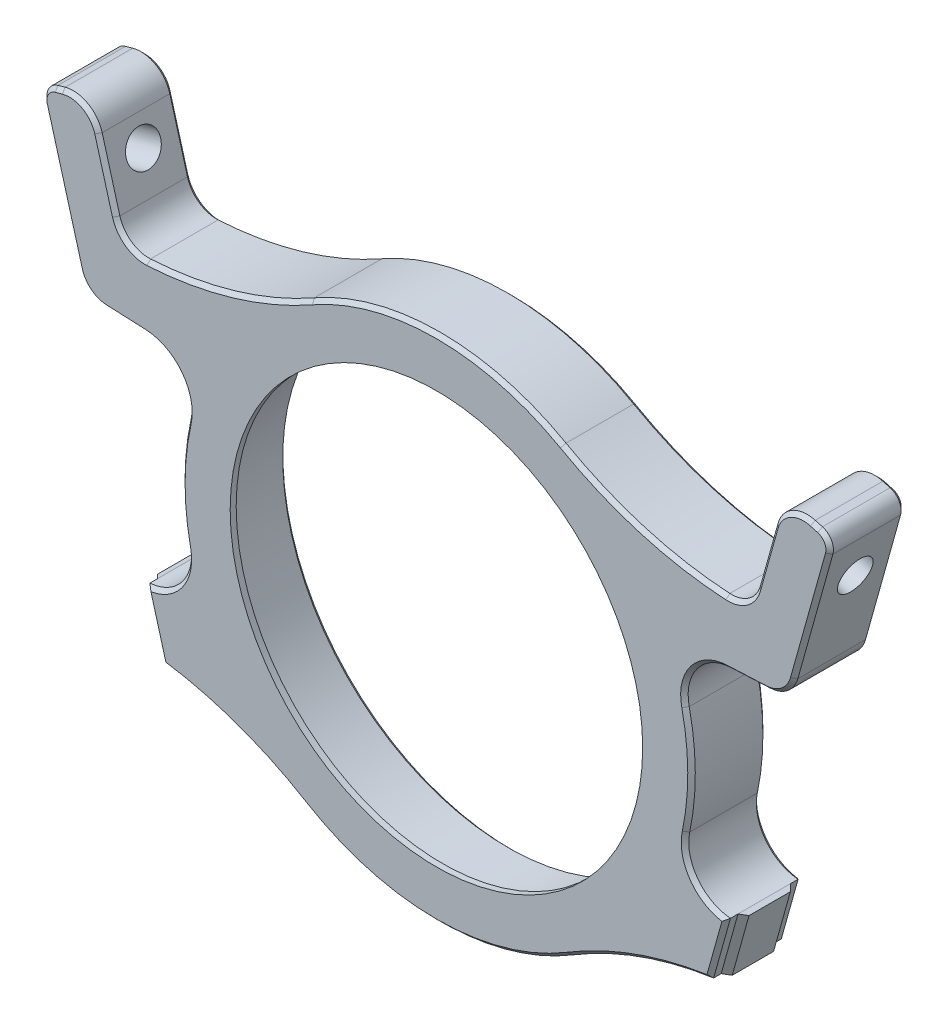
SolidWorks part; units mm, degrees
ref_plane "Ebene vorne" through (0, 0, 0) normal (0, 0, 1) x (1, 0, 0)
ref_plane "Ebene oben" through (0, 0, 0) normal (0, 1, 0) x (1, 0, 0)
ref_plane "Ebene rechts" through (0, 0, 0) normal (1, 0, 0) x (0, 0, -1)
sketch "Skizze1" plane through (0, 0, 0) normal (0, 0, 1) x (1, 0, 0)
  line L0 (-25.6051, -22.2931) -> (-36.3964, -22.2931)
  line L5 (-80.7379, 136.3891) -> (0, -152.5424) construction
  line L6 (-36.3964, -22.2931) -> (-38.6319, -14.2931)
  line L7 (-38.6319, -14.2931) -> (-30.7947, -14.2931)
  line L8 (0, 0) -> (-26.219, 0) construction
  line L9 (0, 0) -> (0, -14.2745) construction
  line L10 (38.6319, -14.2931) -> (30.7947, -14.2931)
  line L11 (36.3964, -22.2931) -> (38.6319, -14.2931)
  line L12 (25.6051, -22.2931) -> (36.3964, -22.2931)
  line L13 (-46.8229, 15.0197) -> (-30.7947, 14.2931)
  line L14 (-25.6051, 22.2931) -> (-41.7923, 23.027)
  line L15 (-46.8229, 15.0197) -> (-49.0328, 22.928)
  line L16 (25.6051, 22.2931) -> (41.7923, 23.027)
  line L17 (46.8229, 15.0197) -> (49.0328, 22.928)
  line L18 (46.8229, 15.0197) -> (30.7947, 14.2931)
  line L19 (80.7379, 136.3891) -> (0, -152.5424) construction
  line L20 (49.0328, 22.928) -> (52.8005, 36.4115)
  line L21 (52.8005, 36.4115) -> (46.0588, 38.2954)
  line L22 (46.0588, 38.2954) -> (41.7923, 23.027)
  line L23 (-49.0328, 22.928) -> (-52.8005, 36.4115)
  line L24 (-52.8005, 36.4115) -> (-46.0588, 38.2954)
  line L25 (-46.0588, 38.2954) -> (-41.7923, 23.027)
  line L26 (52.8005, 36.4115) -> (0, -152.5424) construction
  line L27 (-52.8005, 36.4115) -> (0, -152.5424) construction
  circle A0 centre (0, 0) radius 29.95
  arc A1 (-25.6051, -22.2931) -> (25.6051, -22.2931) centre (0, 0) ccw
  arc A2 (-30.7947, 14.2931) -> (-30.7947, -14.2931) centre (0, 0) ccw
  arc A3 (30.7947, -14.2931) -> (30.7947, 14.2931) centre (0, 0) ccw
  arc A4 (25.6051, 22.2931) -> (-25.6051, 22.2931) centre (0, 0) ccw
  point P24 (0, 0)
  point P32 (-54.7979, 43.5593)
  point P34 (-52.8005, 36.4115)
  dimension "D1" = 59.9
  dimension "D2" = 4
  dimension "D3" = 8
  dimension "D4" = 14
  dimension "D5" = 7
extrude "Aufsatz-Linear austragen1" add sketch "Skizze1" along normal blind 10
sketch "Skizze2" plane through (0, 0, 10) normal (0, 0, 1) x (1, 0, 0)
  circle A0 centre (0, 0) radius 27.45
  circle A1 centre (0, 0) radius 29.95 construction
  circle A2 centre (0, 0) radius 32.75
  dimension "D1" = 2.5
extrude "Aufsatz-Linear austragen2" add sketch "Skizze2" against normal blind 0.8
sketch "Skizze5" plane through (32.7968, -9.1646, 0) normal (-0.9631, 0.2691, 0) x (0, 0, 1)
  line L0 (5, 49.2781) -> (5, 33.95) construction
  line L1 (10, 49.2781) -> (0, 49.2781) construction
  line L3 (10, 33.95) -> (0, 33.95) construction
  circle A0 centre (5, 41.6141) radius 2.3
  point P4 (5, 33.95)
  point P8 (0, 0)
  point P10 (0, 0)
  point P11 (5, 39.7592)
  point P12 (5, 40.272)
  dimension "D1" = 4.6
extrude "Schnitt-Linear austragen1" cut sketch "Skizze5" against normal blind 10
mirror "Spiegeln1" about plane through (0, 0, 0) normal (1, 0, 0) of "Schnitt-Linear austragen1"
fillet "Verrundung1" radius 50 4 edges at (-25.6051, 22.2931, 5) (25.6051, 22.2931, 5) (-25.6051, -22.2931, 5) (25.6051, -22.2931, 5)
fillet "Verrundung2" radius 6 4 edges at (-30.7947, -14.2931, 5) (30.7947, -14.2931, 5) (30.7947, 14.2931, 5) (-30.7947, 14.2931, 5)
fillet "Verrundung3" radius 4 6 edges at (46.0588, 38.2954, 5) (-46.0588, 38.2954, 5) (41.7923, 23.027, 5) (-41.7923, 23.027, 5) (-46.8229, 15.0197, 5) (46.8229, 15.0197, 5)
ref_plane "Ebene1" through (3.1421, -11.2446, 0) normal (-0.2691, 0.9631, 0) x (0, 0, -1)
sketch "Skizze6" plane through (3.1421, -11.2446, 0) normal (-0.2691, 0.9631, 0) x (0, 0, -1)
  line L0 (-5, 41.0532) -> (-5, 46.0217) construction
  line L2 (-8.5, 41.0532) -> (-7.75, 41.8032)
  line L3 (-7.75, 41.8032) -> (-2.25, 41.8032)
  line L4 (-1.5, 41.0532) -> (-2.25, 41.8032)
  line L5 (-1.5, 41.0532) -> (-8.5, 41.0532)
  line L6 (-10, 41.0532) -> (0, 41.0532) construction
  point P2 (-5, 41.0532)
  point P7 (0, 0)
  point P9 (-5, 41.8032)
  point P10 (-8.5, 41.0532)
  point P13 (0, 0)
  dimension "D1" = 45
  dimension "D2" = 7
  dimension "D3" = 0.75
extrude "Aufsatz-Linear austragen3" add sketch "Skizze6" along normal up to vertex (8.3065 mm away)
mirror "Mirror1" about plane through (0, 0, 0) normal (1, 0, 0) of "Aufsatz-Linear austragen3"
fillet "Fillet1" radius 2 2 edges at (-52.8005, 36.4115, 5) (52.8005, 36.4115, 5)
chamfer "Chamfer1" distance 0.5 angle 45 61 edges at (29.95, 0, 0) (-50.3928, 37.0843, 10) (-46.8719, 36.8517, 10) (-43.8061, 30.2337, 10) (-41.1033, 23.8466, 10) (-27.2778, 25.0646, 10) (0, 33.95, 10) (27.2778, 25.0646, 10) (41.1033, 23.8466, 10) (43.8061, 30.2337, 10) (46.8719, 36.8517, 10) (50.3928, 37.0843, 10) (49.9322, 26.1467, 10) (46.2392, 15.7537, 10) (41.3297, 14.7707, 10) (34.2366, 12.3068, 10) (33.9497, 0.1519, 10) (34.2765, -11.9099, 10) (37.5141, -18.2931, 10) (26.661, -24.7136, 10) (0, -33.95, 10) (-26.661, -24.7136, 10) (-37.5141, -18.2931, 10) (-34.2765, -11.9099, 10) (-33.9497, 0.1519, 10) (-34.2366, 12.3068, 10) (-41.3297, 14.7707, 10) (-46.2392, 15.7537, 10) (-49.9322, 26.1467, 10) (-34.2366, 12.3068, 0) (-33.9497, 0.1519, 0) (-34.2765, -11.9099, 0) (-37.5141, -18.2931, 0) (-26.661, -24.7136, 0) (0, -33.95, 0) (26.661, -24.7136, 0) (37.5141, -18.2931, 0) (34.2765, -11.9099, 0) (33.9497, 0.1519, 0) (34.2366, 12.3068, 0) (41.3297, 14.7707, 0) (46.2392, 15.7537, 0) (49.9322, 26.1467, 0) (50.3928, 37.0843, 0) (46.8719, 36.8517, 0) (43.8061, 30.2337, 0) (41.1033, 23.8466, 0) (27.2778, 25.0646, 0) (0, 33.95, 0) (-27.2778, 25.0646, 0) (-41.1033, 23.8466, 0) (-43.8061, 30.2337, 0) (-46.8719, 36.8517, 0) (-50.3928, 37.0843, 0) (-49.9322, 26.1467, 0) (-46.2392, 15.7537, 0) (-41.3297, 14.7707, 0) (52.0787, 36.005, 10) (-52.0787, 36.005, 10) (52.0787, 36.005, 0) (-52.0787, 36.005, 0)
sketch "Skizze7" plane through (0, 0, 0) normal (0, 0, -1) x (-1, 0, 0)
  line L0 (-33.8757, -17.7881) -> (-22.0638, -36.7317)
  line L1 (-22.0638, -36.7317) -> (47.972, -39.4618)
  line L2 (47.972, -39.4618) -> (68.42, 54.1978)
  line L3 (68.42, 54.1978) -> (-64.4084, 52.8049)
  line L4 (-64.4084, 52.8049) -> (-52.1508, -13.7208)
  line L5 (-52.1508, -13.7208) -> (-33.8757, -17.7881)
extrude "Schnitt-Linear austragen2" [suppressed] cut sketch "Skizze7" against normal through all
